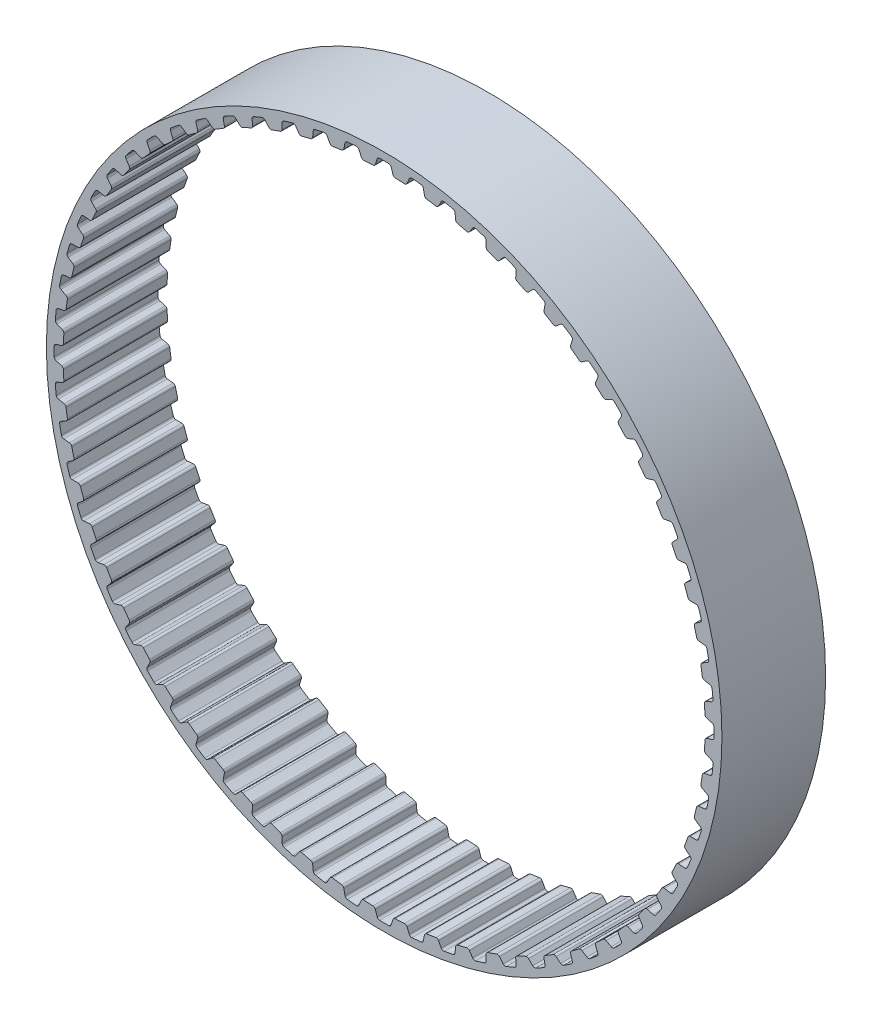
SolidWorks part; units mm, degrees
ref_plane "Front Plane" through (0, 0, 0) normal (0, 0, 1) x (1, 0, 0)
ref_plane "Top Plane" through (0, 0, 0) normal (0, 1, 0) x (1, 0, 0)
ref_plane "Right Plane" through (0, 0, 0) normal (1, 0, 0) x (0, 0, -1)
sketch "Sketch1" plane through (0, 0, 0) normal (0, 0, 1) x (1, 0, 0)
  line L0 (0, 0) -> (-1.2152, 24.735) construction
  line L1 (0, 0) -> (1.2152, 24.735) construction
  line L2 (1.2152, 24.735) -> (-1.2152, 24.735) construction
  line L3 (1.2152, 24.735) -> (-1.2152, 24.735) construction
  line L4 (0, -24.7648) -> (0, -26.0648) construction
  line L5 (0, 0) -> (0, 25.4648) construction
  line L6 (0, 0) -> (-7.392, 24.3683) construction
  circle A0 centre (0, 0) radius 26.0648
  circle A1 centre (0, 0) radius 24.7648
  circle A2 centre (0, 0) radius 25.4648 construction
  dimension "Outer Circle" = 50.9296
  dimension "Angle Distance" = 5.625
  dimension "D1" = 16.875
  dimension "hs" = 1.3
  dimension "ht" = 0.7
sketch "Sketch2" plane through (0, 0, 0) normal (0, 0, 1) x (1, 0, 0)
  line L1 (0, 26.0648) -> (0, 0) construction
  line L2 (-1.25, 25.1097) -> (1.25, 25.1097) construction
  line L4 (-0.7165, 24.7595) -> (-1.7138, 24.7105)
  line L5 (-0.7165, 24.7595) -> (-0.4999, 25.4599)
  line L6 (-1.7138, 24.7105) -> (-1.9981, 25.3863)
  line L7 (0, 0) -> (-1.2152, 24.735) construction
  line L8 (-0.4999, 25.4599) -> (-1.9981, 25.3863) construction
  line L9 (0.4999, 25.4599) -> (1.9981, 25.3863) construction
  line L10 (1.7138, 24.7105) -> (1.9981, 25.3863)
  line L11 (0.7165, 24.7595) -> (0.4999, 25.4599)
  line L12 (0.7165, 24.7595) -> (1.7138, 24.7105)
  line L13 (0, 0) -> (-9.9746, 24.0807) construction
  line L14 (-1.25, 25.1097) -> (-3.7376, 24.8614) construction
  line L15 (-2.4938, 24.9855) -> (0, 0) construction
  line L16 (-3.7376, 24.8614) -> (-3.6817, 24.4896) construction
  line L17 (-1.2152, 24.735) -> (-1.249, 25.4231) construction
  circle A0 centre (0, 0) radius 25.4648 construction
  circle A1 centre (0, 0) radius 25.4648
  circle A2 centre (0, 0) radius 25.1097 construction
  arc A3 (-2.1431, 25.3745) -> (-1.9419, 25.2527) centre (-2.1262, 25.1752) cw
  circle A4 centre (0, 0) radius 26.0648 construction
  circle A5 centre (0, 0) radius 24.7648 construction
  arc A6 (-1.7681, 24.8396) -> (-1.5739, 24.7174) centre (-1.5837, 24.9171) ccw
  arc A7 (-0.3544, 25.4623) -> (-0.5427, 25.3215) centre (-0.3516, 25.2624) ccw
  arc A8 (-0.6751, 24.8933) -> (-0.8564, 24.7526) centre (-0.8662, 24.9524) cw
  point P16 (-0.6082, 25.1097)
  point P20 (0, 25.1097)
  point P43 (1.2152, -24.735)
  point P44 (-9.9746, 24.0807)
  point P45 (1.2152, 24.735)
  point P46 (-1.2152, 24.735)
  point P47 (3.6338, 24.4968)
  point P48 (6.0174, 24.0226)
  point P49 (8.343, 23.3172)
  point P50 (10.5883, 22.3871)
  point P51 (12.7317, 21.2415)
  point P52 (14.7524, 19.8913)
  point P53 (0, 0)
  point P55 (16.631, 18.3495)
  point P56 (18.3495, 16.631)
  point P57 (19.8913, 14.7524)
  point P58 (21.2415, 12.7317)
  point P59 (22.3871, 10.5883)
  point P60 (23.3172, 8.343)
  point P61 (24.0226, 6.0174)
  point P62 (24.4968, 3.6338)
  point P63 (24.735, 1.2152)
  point P64 (24.735, -1.2152)
  point P65 (24.4968, -3.6338)
  point P66 (24.0226, -6.0174)
  point P67 (23.3172, -8.343)
  point P68 (22.3871, -10.5883)
  point P69 (21.2415, -12.7317)
  point P70 (19.8913, -14.7524)
  point P71 (18.3495, -16.631)
  point P72 (16.631, -18.3495)
  point P73 (14.7524, -19.8913)
  point P74 (12.7317, -21.2415)
  point P75 (10.5883, -22.3871)
  point P76 (8.343, -23.3172)
  point P77 (6.0174, -24.0226)
  point P78 (3.6338, -24.4968)
  point P79 (-1.2152, -24.735)
  point P80 (-3.6338, -24.4968)
  point P81 (-6.0174, -24.0226)
  point P82 (-8.343, -23.3172)
  point P83 (-10.5883, -22.3871)
  point P84 (-12.7317, -21.2415)
  point P85 (-14.7524, -19.8913)
  point P86 (-16.631, -18.3495)
  point P87 (-18.3495, -16.631)
  point P88 (-19.8913, -14.7524)
  point P89 (-21.2415, -12.7317)
  point P90 (-22.3871, -10.5883)
  point P91 (-23.3172, -8.343)
  point P92 (-24.0226, -6.0174)
  point P93 (-24.4968, -3.6338)
  point P94 (-24.735, -1.2152)
  point P95 (-24.735, 1.2152)
  point P96 (-24.4968, 3.6338)
  point P97 (-24.0226, 6.0174)
  point P98 (-23.3172, 8.343)
  point P99 (-22.3871, 10.5883)
  point P100 (-21.2415, 12.7317)
  point P101 (-19.8913, 14.7524)
  point P102 (-18.3495, 16.631)
  point P103 (-16.631, 18.3495)
  point P104 (-14.7524, 19.8913)
  point P105 (-12.7317, 21.2415)
  point P106 (-10.5883, 22.3871)
  point P107 (-8.343, 23.3172)
  point P108 (-6.0174, 24.0226)
  point P109 (-3.6338, 24.4968)
  dimension "Teeth Radius" = 0.2
  dimension "b" = 40
  dimension "Pitch" = 2.5
  dimension "D1" = 22.5
  dimension "bt" = 1.5
  dimension "Number of Teeth" = 64
sketch "Sketch3" plane through (0, 0, 0) normal (1, 0, 0) x (0, 0, -1)
  line L0 (-4.0005, 0) -> (4.0005, 0) construction
  line L1 (-4.0005, 25.4648) -> (4.0005, 25.4648) construction
  line L2 (-4.0005, 25.4648) -> (-4.0005, -25.4648) construction
  line L3 (-4.0005, -25.4648) -> (4.0005, -25.4648) construction
  line L4 (4.0005, 25.4648) -> (4.0005, -25.4648) construction
  dimension "D1" = 50.9296
  dimension "Width" = 8.001
sketch "Sketch4" plane through (0, 0, 0) normal (0, 0, 1) x (1, 0, 0)
  circle A0 centre (0, 0) radius 24.7648 construction
  circle A1 centre (0, 0) radius 26.0648 construction
  circle A2 centre (0, 0) radius 24.7648
  circle A3 centre (0, 0) radius 26.0648
extrude "Boss-Extrude1" add sketch "Sketch4" along normal up to vertex (4.0005 mm away) and the other way up to vertex (4.0005 mm away) up to point (0, 25.4648, 4.0005) other way up to point (0, 25.4648, -4.0005)
sketch "Sketch5" plane through (0, 0, 0) normal (0, 0, 1) x (1, 0, 0)
  line L0 (-0.8601, 24.7499) -> (0.8601, 24.7499)
  line L2 (-0.7165, 24.7595) -> (-0.4999, 25.4599) construction
  line L3 (0.7165, 24.7595) -> (0.4999, 25.4599) construction
  line L5 (-0.6759, 24.8907) -> (-0.5427, 25.3215)
  line L7 (0.6759, 24.8907) -> (0.5427, 25.3215)
  arc A0 (0.6759, 24.8907) -> (0.8601, 24.7499) centre (0.867, 24.9498) ccw
  circle A1 centre (0, 0) radius 25.4648 construction
  arc A2 (0.3544, 25.4623) -> (-0.3544, 25.4623) centre (0, 0) ccw
  arc A3 (-0.6759, 24.8907) -> (-0.8601, 24.7499) centre (-0.867, 24.9498) cw
  arc A4 (0.5427, 25.3215) -> (0.3544, 25.4623) centre (0.3516, 25.2624) ccw
  arc A5 (-0.5427, 25.3215) -> (-0.3544, 25.4623) centre (-0.3516, 25.2624) cw
  circle A6 centre (0, 0) radius 24.7648 construction
  arc A7 (-0.8601, 24.7499) -> (0.8601, 24.7499) centre (0, 0) ccw construction
  dimension "D2" = 0.2
extrude "Cut-Extrude1" cut sketch "Sketch5" against normal through all both and the other way through all
pattern_circular "CirPattern1" count 64 over 360 about axis through (0, 0, 4.0005) along (0, 0, 1) of "Cut-Extrude1"
sketch "Sketch6" plane through (0, 0, 4.0005) normal (0, 0, 1) x (1, 0, 0)
  line L0 (0, 25.7648) -> (0, 25.9148) construction
  line L1 (0, 26.0648) -> (0, 0) construction
  line L2 (0, 25.4648) -> (0, 26.0648) construction
  line L3 (0, 25.7648) -> (0, 25.6148) construction
  circle A0 centre (0, 0) radius 25.4648 construction
  circle A1 centre (0, 0) radius 25.9148
  circle A2 centre (0, 0) radius 25.6148
  circle A3 centre (0, 0) radius 26.0648 construction
extrude "Cut-Extrude2" cut sketch "Sketch6" against normal offset from surface (7.401 mm away) 0.3 from offset 0.3 up to face at (0, 0, -4.0005) offset against normal yes
ref_plane "Plane1" through (0, 0, 3.45) normal (0, 0, -1) x (-1, 0, 0)
sketch "Sketch7" plane through (0, 0, 3.45) normal (0, 0, -1) x (-1, 0, 0)
  circle A0 centre (0, 0) radius 25.7648
sweep "Sweep1" add path "Sketch7" circular profile diameter 0.285 parameters "D3"=0.285
pattern_linear "LPattern1" count 24 spacing 0.3 along (0, 0, -1) of bodies 112
equation "\"D1@Sketch3\"= \"Outer Circle@Sketch1\""
equation "\"D1@CirPattern1\" = \"Number of Teeth@Sketch2\""
equation "\"D1@Sketch5\"=\"Teeth Radius@Sketch2\""
equation "\"D2@Sketch5\"=\"Teeth Radius@Sketch2\""
equation "\"D1@Sketch6\"=(\"hs@Sketch1\"-\"ht@Sketch1\")*0.5"
equation "\"D1@Cut-Extrude2\"=\"D1@Sketch6\""
equation "\"D19@Cut-Extrude2\"=\"D1@Sketch6\""
equation "\"COUNT\"= int ( ( \"Width@Sketch3\" - 2 * \"D1@Sketch6\" ) / \"D1@Sketch6\" )"
equation "\"REM\"= ( \"Width@Sketch3\" - 2 * \"D1@Sketch6\" ) - \"COUNT\" * \"D1@Sketch6\""
equation "\"D1@Plane1\"=(\"REM\"+\"D1@Sketch6\")*0.5"
equation "\"D3@Sweep1\"=\"D1@Sketch6\"*0.95"
equation "\"D3@LPattern1\"=\"D1@Sketch6\""
equation "\"D1@LPattern1\"=\"COUNT\""
equation "\"D1@Sketch1\"=\"Angle Distance@Sketch1\"*3"
